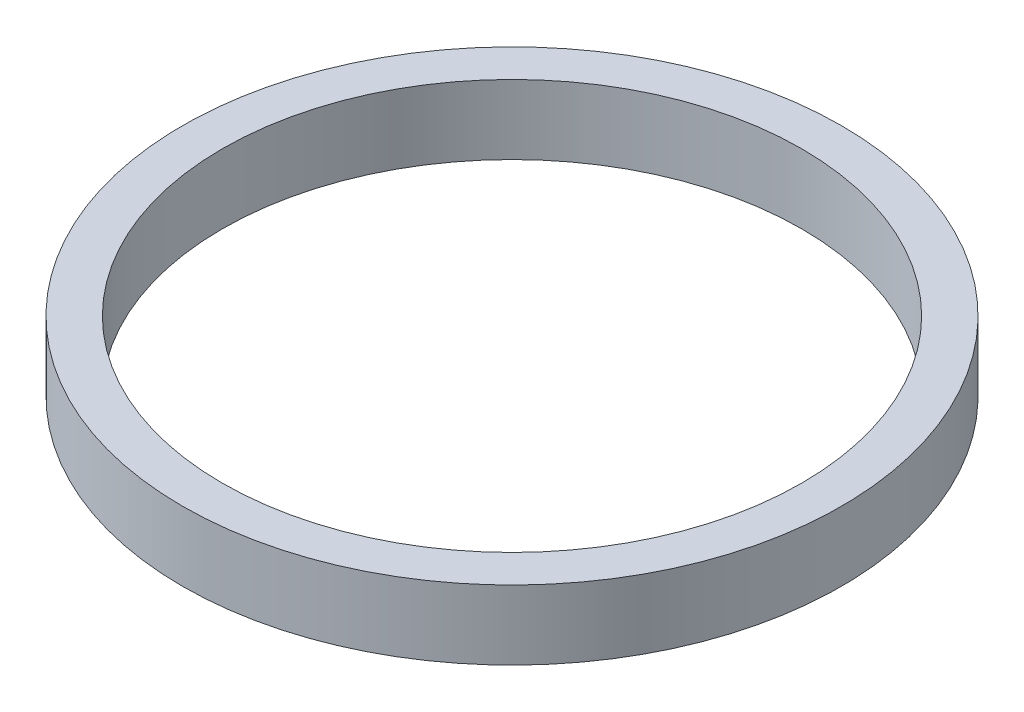
SolidWorks part; units mm, degrees
material "Сосна"
ref_plane "Спереди" through (0, 0, 0) normal (0, 0, 1) x (1, 0, 0)
ref_plane "Сверху" through (0, 0, 0) normal (0, 1, 0) x (1, 0, 0)
ref_plane "Справа" through (0, 0, 0) normal (1, 0, 0) x (0, 0, -1)
sketch "Эскиз1" plane through (0, 0, 0) normal (0, 1, 0) x (1, 0, 0)
  circle A0 centre (0, 0) radius 19
  circle A1 centre (0, 0) radius 16.7
  dimension "D1" = 38
  dimension "D2" = 33.4
extrude "Бобышка-Вытянуть1" add sketch "Эскиз1" along normal blind 4
